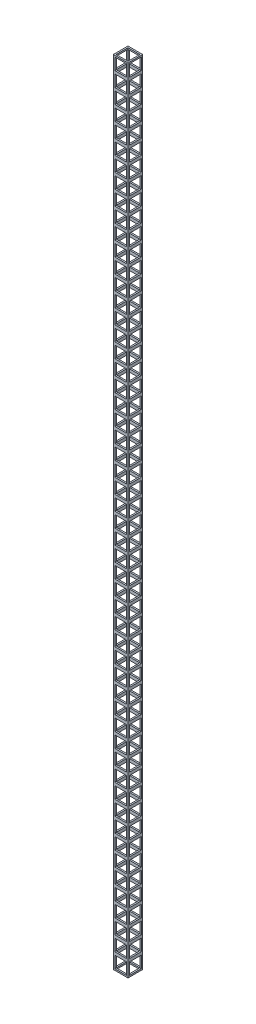
SolidWorks part; units mm, degrees
ref_plane "Ebene vorne" through (0, 0, 0) normal (0, 0, 1) x (1, 0, 0)
ref_plane "Ebene oben" through (0, 0, 0) normal (0, 1, 0) x (1, 0, 0)
ref_plane "Ebene rechts" through (0, 0, 0) normal (1, 0, 0) x (0, 0, -1)
sketch "Skizze1" plane through (0, 0, 0) normal (0, 1, 0) x (1, 0, 0)
  line L1 (0, 0) -> (50, 0)
  line L2 (0, 0) -> (0, 50)
  line L3 (0, 50) -> (50, 50)
  line L4 (50, 0) -> (50, 50)
  dimension "D1" = 50
  dimension "D2" = 50
extrude "Aufsatz-Linear austragen1" add sketch "Skizze1" along normal blind 2700
sketch "Skizze2" plane through (0, 2700, 0) normal (0, 1, 0) x (1, 0, 0)
  line L0 (0, 50) -> (0, 0) construction
  line L1 (5, 45) -> (45, 45)
  line L2 (5, 45) -> (5, 5)
  line L3 (5, 5) -> (45, 5)
  line L4 (45, 45) -> (45, 5)
  line L5 (50, 0) -> (50, 50) construction
  line L6 (50, 50) -> (0, 50) construction
  line L7 (0, 0) -> (50, 0) construction
  dimension "D1" = 5
  dimension "D2" = 5
  dimension "D3" = 5
  dimension "D4" = 5
extrude "Schnitt-Linear austragen1" cut sketch "Skizze2" against normal through all
sketch "Skizze3" plane through (50, 0, 0) normal (1, 0, 0) x (0, 0, -1)
  line L0 (0, 2700) -> (50, 2700) construction
  line L1 (5.1756, 2695) -> (45.1756, 2695)
  line L2 (5.1756, 2695) -> (5.1756, 2655)
  line L3 (5.1756, 2655) -> (45.1756, 2655)
  line L4 (45.1756, 2695) -> (45.1756, 2655)
  dimension "D1" = 5
  dimension "D2" = 40
  dimension "D3" = 40
extrude "Schnitt-Linear austragen2" cut sketch "Skizze3" against normal through all both and the other way through all
pattern_linear "Lineares Muster1" count 54 spacing 50 along (0, -1, 0) of "Schnitt-Linear austragen2"
sketch "Skizze4" plane through (0, 0, -50) normal (0, 0, -1) x (-1, 0, 0)
  line L0 (-50, 2700) -> (0, 2700) construction
  line L5 (-45, 2695) -> (-5, 2695)
  line L6 (-45, 2695) -> (-45, 2655)
  line L7 (-45, 2655) -> (-5, 2655)
  line L8 (-5, 2695) -> (-5, 2655)
  line L9 (-50, 2700) -> (-50, 0) construction
  dimension "D1" = 40
  dimension "D2" = 40
  dimension "D3" = 5
  dimension "D4" = 5
extrude "Schnitt-Linear austragen3" cut sketch "Skizze4" against normal through all both and the other way through all
pattern_linear "Lineares Muster2" count 54 spacing 50 along (0, -1, 0) of "Schnitt-Linear austragen3"
